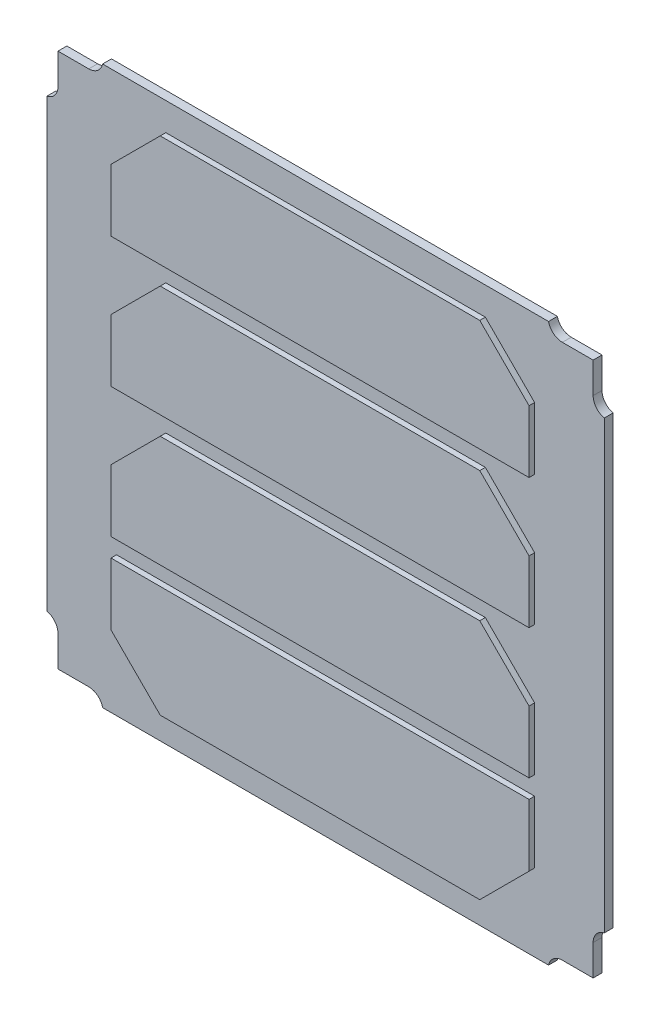
SolidWorks part; units mm, degrees
ref_plane "Front Plane" through (0, 0, 0) normal (0, 0, 1) x (1, 0, 0)
ref_plane "Top Plane" through (0, 0, 0) normal (0, 1, 0) x (1, 0, 0)
ref_plane "Right Plane" through (0, 0, 0) normal (1, 0, 0) x (0, 0, -1)
sketch "Sketch1" plane through (0, 0, 0) normal (0, 0, 1) x (1, 0, 0)
  line L0 (-40, 50) -> (-40, 48)
  line L1 (-50, -50) -> (50, -50)
  line L2 (-50, -50) -> (-50, 50)
  line L3 (-50, 50) -> (50, 50)
  line L4 (50, -50) -> (50, 50)
  line L5 (-50, -50) -> (50, 50) construction
  line L6 (-50, 50) -> (50, -50) construction
  line L7 (-50, 50) -> (-40, 50)
  line L8 (-50, 50) -> (-50, 40)
  line L9 (-40, 48) -> (-48, 48)
  line L10 (-48, 48) -> (-48, 40)
  line L11 (50, 50) -> (40, 50)
  line L12 (50, 50) -> (50, 40)
  line L13 (-48, 40) -> (-50, 40)
  line L14 (50, 40) -> (48, 40)
  line L15 (-50, -50) -> (-37.8649, -50)
  line L16 (-50, -50) -> (-50, -37.8649)
  line L17 (50, 50) -> (50, 40)
  line L18 (50, 50) -> (40, 50)
  line L19 (50, -50) -> (41.5, -50)
  line L20 (50, -50) -> (50, -41.5)
  line L21 (48, 40) -> (48, 48)
  line L22 (48, 48) -> (40, 48)
  line L23 (40, 48) -> (40, 50)
  line L24 (40, -50) -> (40, -48)
  line L25 (50, -50) -> (40, -50)
  line L26 (50, -50) -> (50, -40)
  line L27 (40, -48) -> (48, -48)
  line L28 (48, -48) -> (48, -40)
  line L29 (48, -40) -> (50, -40)
  line L30 (-50, -40) -> (-48, -40)
  line L31 (-50, -50) -> (-50, -40)
  line L32 (-50, -50) -> (-40, -50)
  line L33 (-48, -40) -> (-48, -48)
  line L34 (-48, -48) -> (-40, -48)
  line L35 (-40, -48) -> (-40, -50)
  point P0 (0, 0)
  point P38 (0, 0)
  dimension "D1" = 100
  dimension "D2" = 100
  dimension "D3" = 2
  dimension "D4" = 10
  dimension "D5" = 4
extrude "Boss-Extrude1" add sketch "Sketch1" along normal blind 1.5875 contours L1 L4 L3 L2 region at (0, 0, 0)
sketch "Sketch2" plane through (0, 0, 1.5875) normal (0, 0, 1) x (1, 0, 0)
  line L0 (-28.6612, 45) -> (28.6612, 45)
  line L1 (28.6612, 45) -> (37.5, 36.1612)
  line L2 (37.5, 36.1612) -> (37.5, 25)
  line L3 (37.5, 25) -> (-37.5, 25)
  line L4 (-37.5, 25) -> (-37.5, 36.1612)
  line L5 (-37.5, 36.1612) -> (-28.6612, 45)
  line L6 (0, 0) -> (0, 50) construction
  line L7 (-28.6612, -25) -> (28.6612, -25) construction
  line L8 (-28.6612, 21.6667) -> (28.6612, 21.6667)
  line L9 (28.6612, 21.6667) -> (37.5, 12.8278)
  line L10 (37.5, 12.8278) -> (37.5, 1.6667)
  line L11 (37.5, 1.6667) -> (-37.5, 1.6667)
  line L12 (-37.5, 1.6667) -> (-37.5, 12.8278)
  line L13 (-37.5, 12.8278) -> (-28.6612, 21.6667)
  line L14 (-28.6612, -1.6667) -> (28.6612, -1.6667)
  line L15 (28.6612, -1.6667) -> (37.5, -10.5055)
  line L16 (37.5, -10.5055) -> (37.5, -21.6667)
  line L17 (37.5, -21.6667) -> (-37.5, -21.6667)
  line L18 (-37.5, -21.6667) -> (-37.5, -10.5055)
  line L19 (-37.5, -10.5055) -> (-28.6612, -1.6667)
  line L20 (28.6612, -25) -> (37.5, -33.8388) construction
  line L21 (-50, -11.6667) -> (50, -11.6667) construction
  line L22 (37.5, -33.8388) -> (37.5, -45) construction
  line L23 (37.5, -45) -> (-37.5, -45) construction
  line L24 (-37.5, -36.1612) -> (-28.6612, -45)
  line L25 (-37.5, -25) -> (-37.5, -36.1612)
  line L26 (37.5, -25) -> (-37.5, -25)
  line L27 (37.5, -36.1612) -> (37.5, -25)
  line L28 (28.6612, -45) -> (37.5, -36.1612)
  line L29 (-28.6612, -45) -> (28.6612, -45)
  line L30 (-40, 50) -> (40, 50) construction
  line L31 (-50, -40) -> (-50, 40) construction
  line L32 (50, -40) -> (50, 40) construction
  line L33 (-37.5, -45) -> (-37.5, -33.8388) construction
  line L34 (-37.5, -33.8388) -> (-28.6612, -25) construction
  line L35 (-40, -50) -> (40, -50) construction
  dimension "D1" = 75
  dimension "D2" = 20
  dimension "D3" = 45
  dimension "D4" = 12.5
  dimension "D5" = 5
  dimension "D7" = 5
  dimension "D6" = 4
extrude "Boss-Extrude2" add sketch "Sketch2" along normal blind 1
fillet "Fillet1" radius 2.54 8 edges at (-48, -40, 0.7937) (-40, -48, 0.7937) (40, -48, 0.7937) (48, -40, 0.7937) (48, 40, 0.7937) (40, 48, 0.7937) (-40, 48, 0.7937) (-48, 40, 0.7937)
